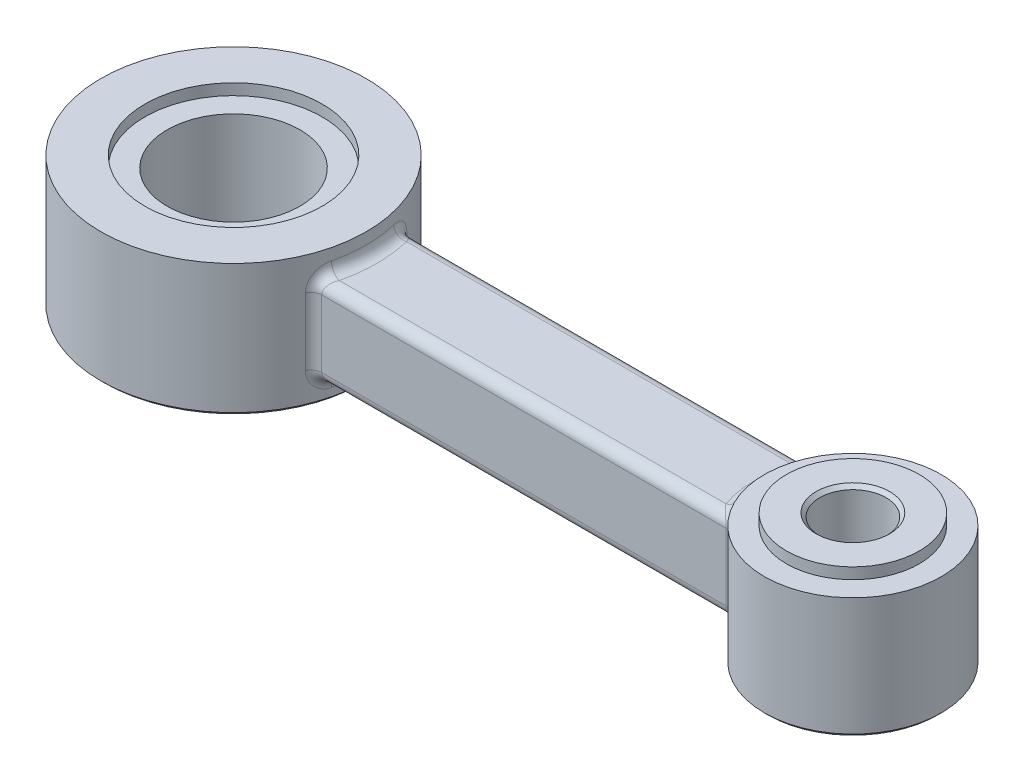
SolidWorks part; units mm, degrees
ref_plane "Front Plane" through (0, 0, 0) normal (0, 0, 1) x (1, 0, 0)
ref_plane "Top Plane" through (0, 0, 0) normal (0, 1, 0) x (1, 0, 0)
ref_plane "Right Plane" through (0, 0, 0) normal (1, 0, 0) x (0, 0, -1)
sketch "Sketch1" plane through (0, 0, 0) normal (0, 1, 0) x (1, 0, 0)
  circle A0 centre (0, 0) radius 19.05
  circle A1 centre (0, 0) radius 9.525
  dimension "D1" = 38.1
  dimension "D2" = 19.05
extrude "Boss-Extrude1" add sketch "Sketch1" along normal blind 19.05
sketch "Sketch2" plane through (0, 0, 0) normal (0, 1, 0) x (1, 0, 0)
  line L0 (0, 0) -> (88.9, 0) construction
  line L1 (44.45, 0) -> (44.45, 17.3831) construction
  circle A0 centre (88.9, 0) radius 12.7
  circle A1 centre (88.9, 0) radius 4.7625
  dimension "D2" = 25.4
  dimension "D3" = 9.525
  dimension "D1" = 88.9
extrude "Boss-Extrude2" add sketch "Sketch2" along normal blind 19.05 separate body
ref_plane "Plane1" through (44.45, 0, 0) normal (1, 0, 0) x (0, 0, -1)
sketch "Sketch3" plane through (0, 19.05, 0) normal (0, 1, 0) x (1, 0, 0)
  circle A0 centre (0, 0) radius 9.525
  circle A1 centre (0, 0) radius 12.7235
  dimension "D1" = 19.05
extrude "Cut-Extrude1" cut sketch "Sketch3" against normal blind 1.6002
sketch "Sketch4" plane through (0, 19.05, 0) normal (0, 1, 0) x (1, 0, 0)
  circle A0 centre (88.9, 0) radius 12.7
  circle A1 centre (88.9, 0) radius 9.525
  dimension "D1" = 19.05
extrude "Cut-Extrude2" cut sketch "Sketch4" against normal blind 1.6002
sketch "Sketch6" plane through (0, 0, 0) normal (0, 1, 0) x (1, 0, 0)
  line L0 (19.05, 0) -> (76.2, 0) construction
  line L1 (17.9605, -6.35) -> (77.9015, -6.35)
  line L2 (17.9605, 6.35) -> (77.9015, 6.35)
  circle A0 centre (0, 0) radius 19.05 construction
  circle A1 centre (88.9, 0) radius 12.7 construction
  arc A2 (17.9605, 6.35) -> (17.9605, -6.35) centre (-0.2008, 0) cw
  arc A3 (77.9015, 6.35) -> (77.9015, -6.35) centre (89.1008, 0) ccw
  dimension "D1" = 6.35
extrude "Boss-Extrude4" add sketch "Sketch6" along normal blind 12.7 from offset 3.175
fillet "Fillet1" radius 1.524 12 edges at (17.9605, 9.525, -6.35) (77.9015, 9.525, -6.35) (47.931, 15.875, 6.35) (19.05, 15.875, 0) (47.931, 15.875, -6.35) (76.2, 15.875, 0) (19.05, 3.175, 0) (47.931, 3.175, 6.35) (76.2, 3.175, 0) (47.931, 3.175, -6.35) (77.9015, 9.525, 6.35) (17.9605, 9.525, 6.35)
chamfer "Chamfer1" distance 0.508 angle 45 3 edges at (88.9, 0, 12.7) (88.9, 19.05, 4.7625) (0, 0, 19.05)
